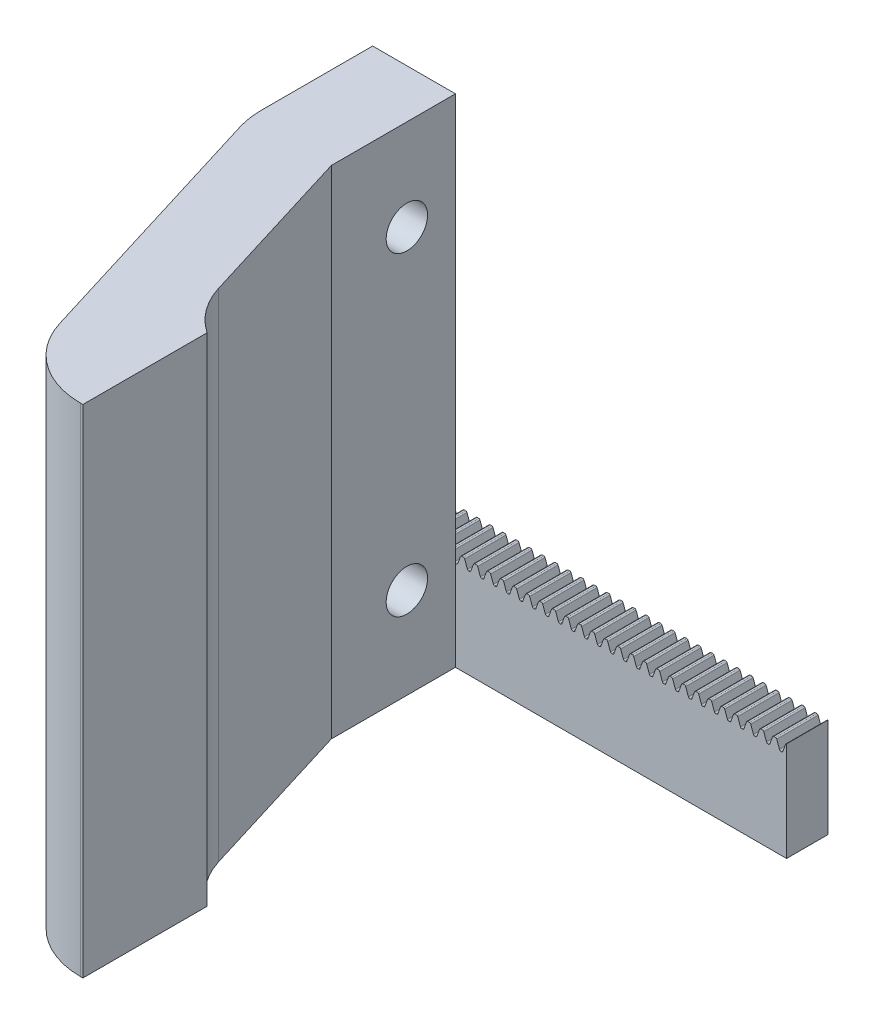
SolidWorks part; units mm, degrees
ref_plane "Front Plane" through (0, 0, 0) normal (0, 0, 1) x (1, 0, 0)
ref_plane "Top Plane" through (0, 0, 0) normal (0, 1, 0) x (1, 0, 0)
ref_plane "Right Plane" through (0, 0, 0) normal (1, 0, 0) x (0, 0, -1)
sketch "Sketch1" plane through (0, 0, 0) normal (0, 0, 1) x (1, 0, 0)
  line L0 (-25, 6) -> (-25, -6) construction
  line L1 (-25, -6) -> (25, -6) construction
  line L2 (25, -6) -> (25, 6) construction
  line L4 (0, 6) -> (0, -6) construction
  line L5 (-25, 5.5) -> (25, 5.5) construction
  line L6 (-23.7727, 6) -> (-23.3512, 6) construction
  line L7 (-23.3512, 6) -> (-22.9418, 4.875) construction
  line L8 (-23.7727, 6) -> (-24.1821, 4.875) construction
  line L9 (-24.1821, 4.875) -> (-22.9418, 4.875) construction
  line L10 (-23.5619, 6) -> (-23.5619, 4.875) construction
  line L11 (-25, 0) -> (-20.4204, 0) construction
  line L12 (25, 0) -> (20.4204, 0) construction
  point P15 (-21.9911, 6)
  point P16 (-15.5, -6)
  point P17 (-23.1692, 5.5)
  point P18 (-23.9546, 5.5)
  point P21 (-0.25, -6)
  dimension "Length" = 50
  dimension "Height" = 12
  dimension "Approximate Number of Teeth" = 31
  dimension "Pressure Angle" = 20
  dimension "Circular Pitch" = 1.5708
  dimension "Addendum" = 0.5
  dimension "Dedendum" = 0.625
  dimension "Circular Tooth Thickness" = 0.7854
  dimension "Module" = 0.5
  dimension "Rack Length" = 47.1239
  dimension "D1" = 3.1416
sketch "Sketch2" plane through (0, 0, 0) normal (1, 0, 0) x (0, 0, -1)
  line L0 (-2.5, 0) -> (2.5, 0) construction
  dimension "Face Width" = 5
sketch "Sketch3" plane through (0, 0, 0) normal (0, 0, 1) x (1, 0, 0)
  line L1 (-25, 6) -> (25, 6)
  line L2 (-25, 6) -> (-25, -6)
  line L3 (-25, -6) -> (25, -6)
  line L4 (25, 6) -> (25, -6)
extrude "Boss-Extrude1" add sketch "Sketch3" against normal up to vertex (2.5 mm away) and the other way up to vertex (2.5 mm away) up to point (0, 0, -2.5) other way up to point (0, 0, 2.5)
sketch "Sketch4" plane through (0, 0, 0) normal (0, 0, 1) x (1, 0, 0)
  line L0 (-23.5619, 6) -> (-21.9911, 6) construction
  line L9 (-22.7765, 6) -> (-22.7765, 4.875)
  line L10 (-22.7765, 4.875) -> (-22.9418, 4.875)
  line L11 (-22.9418, 4.875) -> (-23.3512, 6)
  line L12 (-23.3512, 6) -> (-22.7765, 6)
  line L13 (-23.7727, 6) -> (-24.1821, 4.875)
  line L14 (-24.1821, 4.875) -> (-24.3473, 4.875)
  line L15 (-24.3473, 4.875) -> (-24.3473, 6)
  line L16 (-24.3473, 6) -> (-23.7727, 6)
  line L17 (25, 6) -> (-25, 6) construction
  line L18 (-23.7727, 6) -> (-23.6552, 6)
  line L19 (-23.4687, 6) -> (-23.3512, 6)
  arc A0 (-24.2996, 4.875) -> (-24.142, 4.9854) centre (-24.2996, 5.0428) ccw
  arc A1 (-22.9819, 4.9854) -> (-22.8243, 4.875) centre (-22.8243, 5.0428) ccw
  arc A2 (-23.8128, 5.8896) -> (-23.6552, 6) centre (-23.6552, 5.8322) cw
  arc A3 (-23.4687, 6) -> (-23.3111, 5.8896) centre (-23.4687, 5.8322) cw
  dimension "D1" = 0.1678
extrude "Cut-Extrude1" cut sketch "Sketch4" against normal through all both and the other way through all contours L14 A0 L13 L16 L15 | L13 A2 L18 | L19 A3 L11 | L11 A1 L10 L9 L12 region at (-22.9807, 5.5452, 0) region at (-23.3677, 5.9764, 0) region at (-23.7562, 5.9764, 0) region at (-24.1431, 5.5452, 0)
pattern_linear "LPattern1" count 32 spacing 1.5708 along (1, 0, 0) count 2 spacing 1.5708 along (-1, 0, 0) of "Cut-Extrude1"
sketch "Drawing Refernce 1" plane through (0, 0, 2.5) normal (0, 0, 1) x (1, 0, 0)
  line L0 (-25, 0) -> (25, 0) construction
  point P6 (-10, 0)
  point P7 (-2.5, 0)
  point P8 (10, 0)
  dimension "D1" = 15
  dimension "D2" = 22.5
  dimension "D3" = 15
sketch "Sketch5" plane through (0, 0, 2.5) normal (0, 0, 1) x (1, 0, 0)
  line L1 (-25, -6) -> (-15, -6)
  line L2 (-25, -6) -> (-25, 54)
  line L3 (-25, 54) -> (-15, 54)
  line L4 (-15, -6) -> (-15, 54)
  dimension "D1" = 60
  dimension "D2" = 10
extrude "Boss-Extrude2" add sketch "Sketch5" along normal blind 15
sketch "Sketch6" plane through (0, 0, 17.5) normal (0, 0, 1) x (1, 0, 0)
  line L0 (-25, -6) -> (-15, -6) construction
  line L1 (-25, 54) -> (-5, 54)
  line L2 (-25, 54) -> (-25, -6)
  line L3 (-25, -6) -> (-5, -6)
  line L4 (-5, 54) -> (-5, -6)
  dimension "D1" = 20
extrude "Boss-Extrude3" add sketch "Sketch6" along normal blind 40
sketch "Sketch7" plane through (0, -6, 0) normal (0, -1, 0) x (1, 0, 0)
  line L0 (-12.7027, 57.5) -> (-25, 17.5)
  line L1 (-25, 57.5) -> (-5, 57.5) construction
  line L2 (-25, -2.5) -> (-25, 57.5) construction
  line L3 (-12.7027, 57.5) -> (-25, 57.5)
  line L4 (-25, 57.5) -> (-25, 17.5)
  line L5 (-15, 17.5) -> (-7.3142, 42.5)
  line L6 (-7.3142, 42.5) -> (-5, 42.5)
  line L7 (-5, 57.5) -> (-5, 17.5) construction
  line L8 (-15, 17.5) -> (-5, 17.5) construction
  line L9 (-5, 42.5) -> (-5, 17.5)
  line L10 (-5, 17.5) -> (-15, 17.5)
  line L11 (-15, 2.5) -> (25, 2.5) construction
  dimension "D1" = 25
  dimension "D2" = 15
extrude "Cut-Extrude2" cut sketch "Sketch7" against normal up to surface (60 mm away) up to face at (-15, 54, 25.8333)
fillet "Fillet3" radius 10 1 edges at (-25, 24, 17.5)
fillet "Fillet4" radius 10 1 edges at (-12.7027, 24, 57.5)
fillet "Fillet5" radius 10 1 edges at (-7.3142, 24, 42.5)
sketch "Sketch8" plane through (-25, 0, 0) normal (-1, 0, 0) x (0, 0, 1)
  line L1 (-2.5, 5.9953) -> (-2.5, -6) construction
  line L2 (50.4386, 24) -> (-4.6559, 24) construction
  line L3 (50.4386, -6) -> (50.4386, 54) construction
  circle A0 centre (8.367, 43) radius 2.5
  circle A1 centre (8.367, 5) radius 2.5
  dimension "D1" = 5
  dimension "D2" = 5
  dimension "D3" = 19
  dimension "D4" = 19
  dimension "D5" = 10.867
extrude "Cut-Extrude3" cut sketch "Sketch8" against normal through all
equation "\"Diametral Pitch\"= 1 / \"Module\""
equation "\"Pressure Angle\"=20"
equation "\"Dedendum\"= 1.25 / \"Diametral Pitch\""
equation "\"Addendum\"= 1 / \"Diametral Pitch\""
equation "\"WorkingDepth\"= 2 / \"Diametral Pitch\""
equation "\"WholeDepth\"= 2.25 / \"Diametral Pitch\""
equation "\"Clearance\"= 0.25 / \"Diametral Pitch\""
equation "\"ToothThickness\"= ( pi / 2 ) / \"Diametral Pitch\""
equation "\"CircularPitch\"= pi / \"Diametral Pitch\""
equation "\"Fillet\"= \"Clearance\" * cos ( \"Pressure Angle\" ) * tan ( ( 90 + \"Pressure Angle\" ) / 2 )"
equation "\"Module\"= 0.5"
equation "\"Addendum@Sketch1\"=\"Addendum\""
equation "\"Pressure Angle@Sketch1\"=\"Pressure Angle\""
equation "\"Dedendum@Sketch1\"=\"Dedendum\""
equation "\"Circular Pitch@Sketch1\"=\"CircularPitch\""
equation "\"Circular Tooth Thickness@Sketch1\"=\"ToothThickness\""
equation "\"Module@Sketch1\"=\"Module\""
equation "\"Approximate Number of Teeth@Sketch1\" = int ( \"Length@Sketch1\" /  ( 2 * \"Circular Tooth Thickness@Sketch1\" )  ) "
equation "\"Rack Length@Sketch1\" = \"Circular Pitch@Sketch1\" *  ( \"Approximate Number of Teeth@Sketch1\" - 1 ) "
equation "\"D3@LPattern1\"=\"CircularPitch\""
equation "\"D1@LPattern1\"=\"Approximate Number of Teeth@Sketch1\"+1"
equation "\"D1@Sketch1\"=\"Circular Pitch@Sketch1\"*2"
equation "\"D1@Sketch4\"=\"Fillet\""
equation "\"D4@LPattern1\"=\"CircularPitch\""
equation "\"D2@Drawing Refernce 1\"=\"D1@Drawing Refernce 1\"*1.5"
equation "\"D3@Drawing Refernce 1\"=\"D1@Drawing Refernce 1\""
